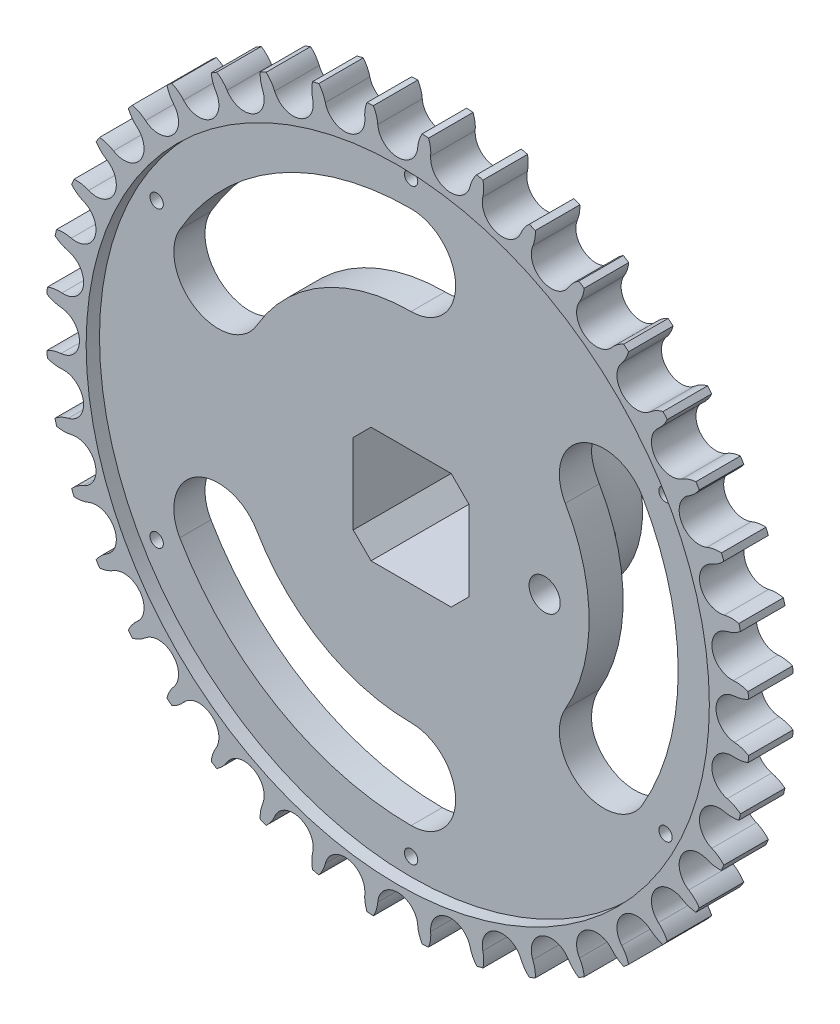
SolidWorks part; units mm, degrees
ref_plane "Front Plane" through (0, 0, 0) normal (0, 0, 1) x (1, 0, 0)
ref_plane "Top Plane" through (0, 0, 0) normal (0, 1, 0) x (1, 0, 0)
ref_plane "Right Plane" through (0, 0, 0) normal (1, 0, 0) x (0, 0, -1)
sketch "Sketch1" plane through (0, 0, 0) normal (0, 0, 1) x (1, 0, 0)
  circle A0 centre (0, 0) radius 39.5
  dimension "D1" = 79
extrude "Boss-Extrude1" add sketch "Sketch1" along normal blind 5
sketch "Sketch2" plane through (0, 0, 5) normal (0, 0, 1) x (1, 0, 0)
  line L0 (4.5, 6.5) -> (6.5, 4.5)
  line L1 (-4.5, -6.5) -> (4.5, -6.5)
  line L2 (-6.5, -4.5) -> (-6.5, 4.5)
  line L3 (-4.5, 6.5) -> (4.5, 6.5)
  line L4 (6.5, -4.5) -> (6.5, 4.5)
  line L5 (-6.5, -6.5) -> (6.5, 6.5) construction
  line L6 (-6.5, 6.5) -> (6.5, -6.5) construction
  line L7 (-6.5, 4.5) -> (-4.5, 6.5)
  line L8 (-6.5, -4.5) -> (-4.5, -6.5)
  line L9 (4.5, -6.5) -> (6.5, -4.5)
  point P0 (0, 0)
  dimension "D1" = 13
  dimension "D2" = 13
extrude "Cut-Extrude1" cut sketch "Sketch2" against normal blind 5
sketch "Sketch3" plane through (0, 0, 0) normal (0, 0, -1) x (-1, 0, 0)
  line L0 (6.5, -4.5) -> (4.5, -6.5) construction
  line L1 (4.5, -6.5) -> (-4.5, -6.5) construction
  line L2 (-4.5, -6.5) -> (-6.5, -4.5) construction
  line L3 (-6.5, -4.5) -> (-6.5, 4.5) construction
  line L4 (-6.5, 4.5) -> (-4.5, 6.5) construction
  line L5 (4.5, 6.5) -> (6.5, 4.5) construction
  line L6 (6.5, 4.5) -> (6.5, -4.5) construction
  line L7 (-4.5, 6.5) -> (4.5, 6.5) construction
  line L8 (6.5, -4.5) -> (4.5, -6.5)
  line L9 (4.5, -6.5) -> (-4.5, -6.5)
  line L10 (-4.5, -6.5) -> (-6.5, -4.5)
  line L11 (-6.5, -4.5) -> (-6.5, 4.5)
  line L12 (-6.5, 4.5) -> (-4.5, 6.5)
  line L13 (4.5, 6.5) -> (6.5, 4.5)
  line L14 (6.5, 4.5) -> (6.5, -4.5)
  line L15 (-4.5, 6.5) -> (4.5, 6.5)
  circle A0 centre (0, 0) radius 12.5
  dimension "D1" = 25
extrude "Boss-Extrude2" add sketch "Sketch3" along normal blind 10
fillet "Fillet1" radius 10 1 edges at (12.5, 0, 0)
sketch "Sketch4" plane through (0, 0, 5) normal (0, 0, 1) x (1, 0, 0)
  line L0 (-21.6506, 12.5) -> (0, 0) construction
  line L1 (0, 0) -> (0, 25) construction
  arc A0 (-21.6506, 12.5) -> (0, 25) centre (0, 0) cw construction
  arc A1 (0, 30) -> (-25.9808, 15) centre (0, 0) ccw
  arc A2 (0, 20) -> (-17.3205, 10) centre (0, 0) ccw
  arc A3 (0, 20) -> (0, 30) centre (0, 25) ccw
  arc A4 (-25.9808, 15) -> (-17.3205, 10) centre (-21.6506, 12.5) ccw
  arc A5 (17.3205, -10) -> (17.3205, 10) centre (0, 0) ccw
  arc A6 (17.3205, -10) -> (25.9808, -15) centre (21.6506, -12.5) ccw
  arc A7 (25.9808, 15) -> (17.3205, 10) centre (21.6506, 12.5) ccw
  arc A8 (25.9808, -15) -> (25.9808, 15) centre (0, 0) ccw
  arc A9 (21.6506, 12.5) -> (21.6506, -12.5) centre (0, 0) cw construction
  arc A10 (-17.3205, -10) -> (0, -20) centre (0, 0) ccw
  arc A11 (-17.3205, -10) -> (-25.9808, -15) centre (-21.6506, -12.5) ccw
  arc A12 (0, -30) -> (0, -20) centre (0, -25) ccw
  arc A13 (-25.9808, -15) -> (0, -30) centre (0, 0) ccw
  arc A14 (0, -25) -> (-21.6506, -12.5) centre (0, 0) cw construction
  point P4 (-12.5, 21.6506)
  point P17 (25, 0)
  point P24 (-12.5, -21.6506)
  point P29 (0, 0)
  dimension "D1" = 25
  dimension "D2" = 5
  dimension "D3" = 60
  dimension "D4" = 3
extrude "Cut-Extrude2" cut sketch "Sketch4" against normal blind 10
sketch "Sketch5" plane through (0, 0, 5) normal (0, 0, 1) x (1, 0, 0)
  circle A0 centre (0, 0) radius 35
  dimension "D1" = 70
extrude "Cut-Extrude3" cut sketch "Sketch5" against normal blind 1.5
sketch "Sketch7" plane through (0, 0, 5) normal (0, 0, 1) x (1, 0, 0)
  line L0 (0, 0) -> (0, 38) construction
  line L1 (0, 0) -> (5.9445, 37.5322) construction
  line L2 (0, 0) -> (-5.9445, 37.5322) construction
  circle A0 centre (0, 38) radius 2.25
  circle A1 centre (5.9445, 37.5322) radius 2.25 construction
  arc A2 (3.1459, 39.9721) -> (2.2431, 37.8235) centre (5.9445, 37.5322) ccw construction
  circle A3 centre (-5.9445, 37.5322) radius 2.25 construction
  arc A4 (-3.1459, 39.9721) -> (-2.2431, 37.8235) centre (-5.9445, 37.5322) cw construction
  arc A6 (3.1459, 39.9721) -> (-3.1459, 39.9721) centre (0, 38) ccw
  arc A7 (-2.2431, 37.8235) -> (-3.1459, 39.9721) centre (-5.9445, 37.5322) ccw
  arc A8 (3.1459, 39.9721) -> (2.2431, 37.8235) centre (5.9445, 37.5322) ccw
  circle M2 centre (0, 0) radius 39.5
  dimension "D2" = 4.5
  dimension "D4" = 4.5
  dimension "D1" = 38
  dimension "D3" = 9
extrude "Cut-Extrude4" cut sketch "Sketch7" against normal blind 5 contours A0 M2 | A8 A0 M2 | A7 A0 M2 region at (0, 37.773, 5) region at (-2.2572, 39.0406, 5) region at (2.2572, 39.0406, 5)
pattern_circular "CirPattern1" count 40 over 360 about axis through (0, 0, 5) along (0, 0, 1) of "Cut-Extrude4"
sketch "Sketch8" plane through (0, 0, 0) normal (0, 0, 1) x (1, 0, 0)
  line L0 (0, 0) -> (0, 44.882) construction
  circle A0 centre (0, 33) radius 0.75
  circle A1 centre (15, 0) radius 1.75
  circle A2 centre (28.5788, 16.5) radius 0.75
  circle A3 centre (28.5788, -16.5) radius 0.75
  circle A4 centre (0, -33) radius 0.75
  circle A5 centre (-28.5788, -16.5) radius 0.75
  circle A6 centre (-28.5788, 16.5) radius 0.75
  point P20 (0, 0)
  dimension "D1" = 3.5
  dimension "D2" = 1.5
  dimension "D3" = 15
  dimension "D4" = 33
  dimension "D5" = 6
extrude "Cut-Extrude5" cut sketch "Sketch8" along normal through all both and the other way through all
